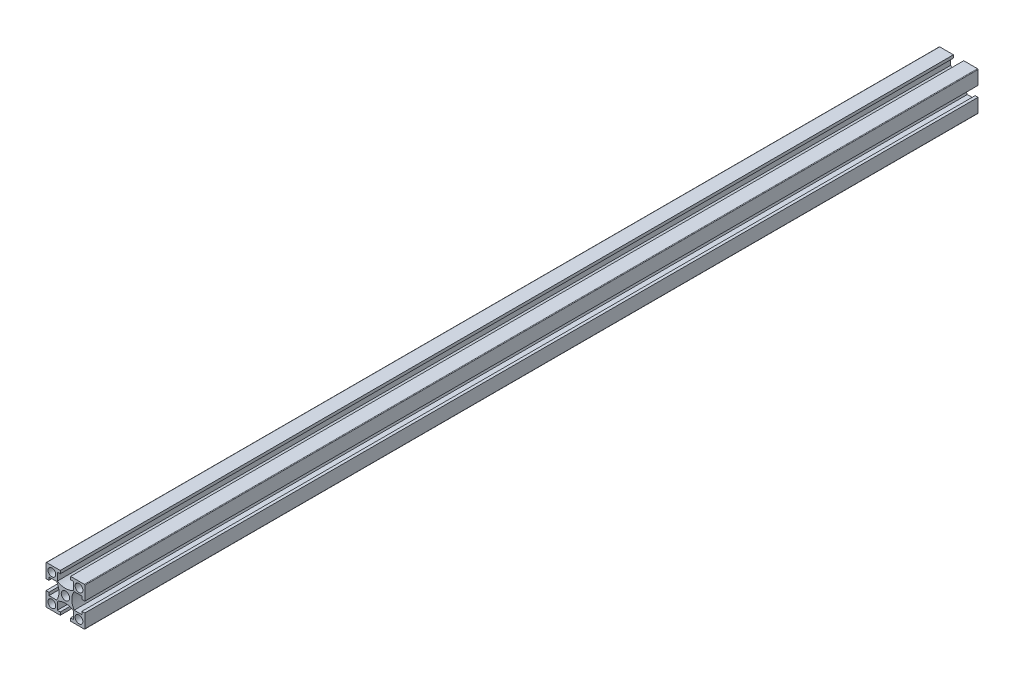
SolidWorks part; units mm, degrees
material "3.0255 (EN-AW 1350A)"
ref_plane "정면" through (0, 0, 0) normal (0, 0, 1) x (1, 0, 0)
ref_plane "윗면" through (0, 0, 0) normal (0, 1, 0) x (1, 0, 0)
ref_plane "우측면" through (0, 0, 0) normal (1, 0, 0) x (0, 0, -1)
sketch "스케치1" plane through (0, 0, 0) normal (0, 0, 1) x (1, 0, 0)
  line L0 (0, 32.0265) -> (0, -31.6588) construction
  line L1 (-10, 10) -> (-10, -10)
  line L2 (-10, 10) -> (10, 10)
  line L3 (-10, 2.65) -> (-8.5, 2.65)
  line L4 (13.6618, 0) -> (-11.6993, 0) construction
  line L5 (-8.5, 2.65) -> (-8.5, 4.15)
  line L6 (-8.5, 4.15) -> (-4.5032, 4.15)
  line L7 (-10, -2.65) -> (-8.5, -2.65)
  line L8 (-8.5, -2.65) -> (-8.5, -4.15)
  line L9 (-8.5, -4.15) -> (-4.5032, -4.15)
  line L10 (-10, -10) -> (10, -10)
  line L11 (10, 10) -> (10, -10)
  circle A0 centre (-7, 7) radius 2
  circle A1 centre (-7, -7) radius 2
  arc A2 (-4.5032, 4.15) -> (-4.5032, -4.15) centre (-11.0587, 0) cw
  circle A3 centre (0, 0) radius 2.15
  circle A4 centre (7, 7) radius 2
  circle A5 centre (7, -7) radius 2
  point P21 (-10, 0)
  point P23 (-3.3, 0)
  point P31 (0, -10)
  point P32 (0, 10)
  dimension "D3" = 4
  dimension "D9" = 6.7
  dimension "D10" = 4.3
  dimension "D11" = 7.7587
  dimension "D1" = 20
  dimension "D2" = 20
  dimension "D4" = 14
  dimension "D5" = 14
  dimension "D6" = 5.3
  dimension "D7" = 8.3
  dimension "D8" = 1.5
extrude "보스-돌출1" add sketch "스케치1" along normal blind 460 contours A0 | A4 | A3 | A5 | A1 | A2 L6 L5 L3 L1 L7 L8 L9 | L2 L11 L10 L1 region at (-6.6069, 0, 0) region at (-7, 7, 0) region at (-7, -7, 0) region at (0, 0, 0) region at (7, 7, 0) region at (7, -7, 0)
extrude "컷-돌출1" cut sketch "스케치1<3>" along normal up to next contours A2 L6 L5 L3 L1 L7 L8 L9 region at (-6.6069, 0, 0)
sketch "스케치1<3>" plane through (0, 0, 0) normal (0, 0, 1) x (1, 0, 0) same geometry as "스케치1"
pattern_circular "원형 패턴1" count 4 over 360 about axis through (0, 0, 460) along (0, 0, -1) of "컷-돌출1" reverse direction yes
fillet "필렛1" radius 0.3 4 edges at (10, -10, 230) (-10, -10, 230) (-10, 10, 230) (10, 10, 230)
sketch "스케치3" plane through (0, 10, 0) normal (0, 1, 0) x (1, 0, 0)
  line L0 (4.15, 0) -> (-4.15, 0) construction
  line L1 (-4.15, -460) -> (4.15, -460) construction
  circle A0 centre (0, -10) radius 2.15
  circle A1 centre (0, -450) radius 2.15
  dimension "D1" = 10
  dimension "D2" = 10
  dimension "D3" = 4.3
  dimension "D4" = 4.3
extrude "컷-돌출3" cut sketch "스케치3" against normal through all
sketch "스케치4" plane through (-10, 0, 0) normal (-1, 0, 0) x (0, 0, 1)
  line L0 (460, -2.65) -> (460, -9.7) construction
  circle A0 centre (10, 0) radius 2.15
  circle A1 centre (450, 0) radius 2.15
  dimension "D1" = 4.3
  dimension "D2" = 10
  dimension "D3" = 10
extrude "컷-돌출4" cut sketch "스케치4" against normal through all
sketch "스케치5" plane through (-10, 0, 0) normal (-1, 0, 0) x (0, 0, 1)
  line L0 (20, 9.7) -> (20, -9.7) construction
  line L1 (460, 9.7) -> (0, 9.7) construction
  line L2 (0, -9.7) -> (460, -9.7) construction
  line L3 (440, 9.7) -> (440, -9.7) construction
  line L4 (460, -2.65) -> (460, -9.7) construction
  line L5 (0, -2.65) -> (0, -9.7) construction
  line L6 (180.5, 9.7) -> (180.5, -9.7) construction
  line L7 (279.5, 9.7) -> (279.5, -9.7) construction
  circle A0 centre (190.5, 0) radius 2.5
  circle A1 centre (269.5, 0) radius 2.5
  dimension "D3" = 160.5
  dimension "D6" = 10
  dimension "D1" = 20
  dimension "D2" = 20
  dimension "D4" = 10
  dimension "D5" = 160.5
extrude "컷-돌출5" cut sketch "스케치5" against normal through all
sketch "스케치6" plane through (0, -10, 0) normal (0, -1, 0) x (1, 0, 0)
  line L0 (2.65, 0) -> (9.7, 0) construction
  line L1 (2.65, 460) -> (9.7, 460) construction
  circle A0 centre (0, 190.5) radius 2.5
  circle A1 centre (0, 269.5) radius 2.5
  dimension "D1" = 190.5
  dimension "D2" = 190.5
extrude "컷-돌출9" cut sketch "스케치6" against normal blind 7
